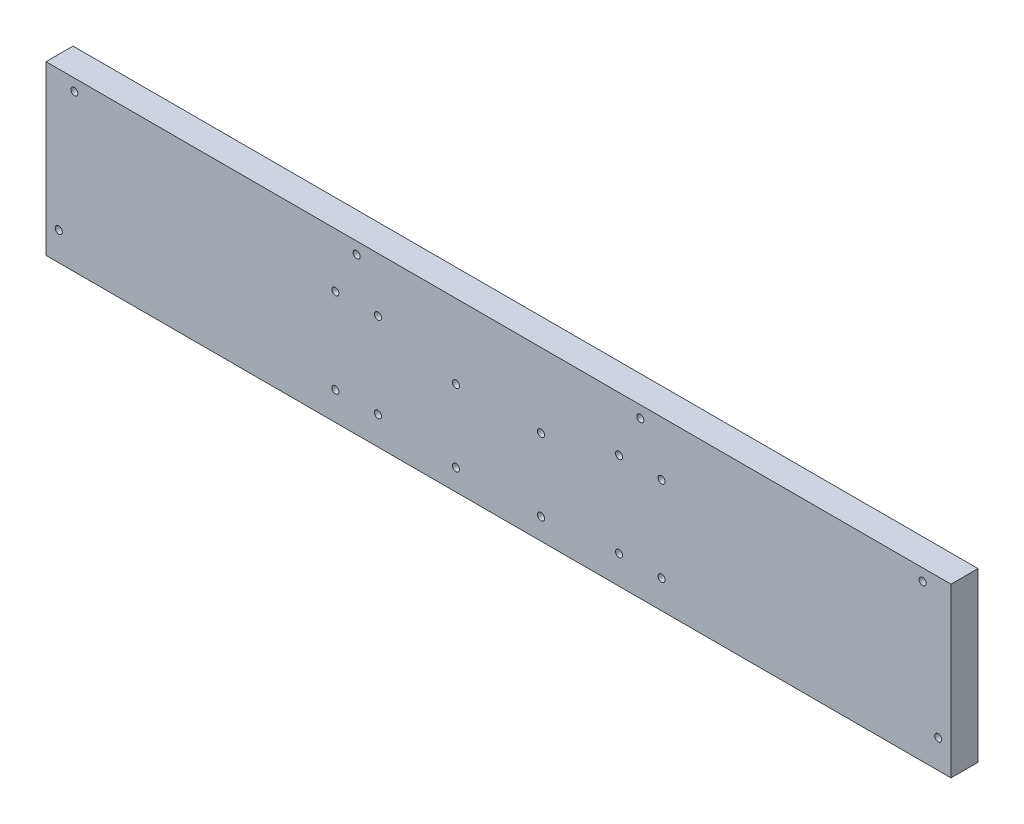
SolidWorks part; units mm, degrees
ref_plane "Front Plane" through (0, 0, 0) normal (0, 0, 1) x (1, 0, 0)
ref_plane "Top Plane" through (0, 0, 0) normal (0, 1, 0) x (1, 0, 0)
ref_plane "Right Plane" through (0, 0, 0) normal (1, 0, 0) x (0, 0, -1)
sketch "Sketch1" plane through (0, 0, 0) normal (0, 0, 1) x (1, 0, 0)
  line L1 (0, 118.3) -> (-638.1, 118.3)
  line L2 (0, 118.3) -> (0, 0)
  line L3 (0, 0) -> (-638.1, 0)
  line L4 (-638.1, 118.3) -> (-638.1, 0)
  dimension "D1" = 118.3
  dimension "D2" = 638.1
extrude "Boss-Extrude1" add sketch "Sketch1" along normal blind 19.05
sketch "Sketch4" plane through (0, 0, 19.05) normal (0, 0, 1) x (1, 0, 0)
  line L0 (-638.1, 0) -> (-638.1, 118.3)
  line L1 (-319.05, 0) -> (-319.05, 58.68)
  line L2 (-638.1, 0) -> (0, 0) construction
  line L3 (-638.1, 59.15) -> (0, 59.15)
  line L4 (0, 0) -> (0, 118.3) construction
  circle A6 centre (-9, 20) radius 2.5
  circle A7 centre (-20, 110.05) radius 2.5
  circle A8 centre (-219.05, 110.05) radius 2.5
  circle A9 centre (-419.05, 110.05) radius 2.5
  circle A10 centre (-618.1, 110.05) radius 2.5
  circle A11 centre (-629.1, 20) radius 2.5
hole_wizard "Ø5.0mm Dowel Hole1" positions "Sketch2" profile "Sketch3" hole size "Ø5.0" standard "ANSI Metric"
sketch "Sketch2" plane through (0, 0, 0) normal (0, 0, -1) x (-1, 0, 0)
  point P0 (434.05, 20)
  point P3 (404.05, 20)
  point P6 (404.05, 80)
  point P9 (434.05, 80)
  point P12 (349.05, 15)
  point P15 (349.05, 66)
  point P18 (289.05, 66)
  point P25 (289.05, 15)
  point P28 (234.05, 20)
  point P31 (234.05, 80)
  point P34 (204.05, 80)
  point P37 (204.05, 20)
  point P40 (629.1, 20)
  point P43 (618.1, 110.05)
  point P46 (419.05, 110.05)
  point P49 (219.05, 110.05)
  point P52 (20, 110.05)
  point P55 (9, 20)
sketch "Sketch3" plane through (-434.05, 20, 0) normal (1, 0, 0) x (0, 1, 0)
  line L0 (0, 0) -> (0, 30)
  line L1 (0, 30) -> (2.5, 28.4978)
  line L2 (2.5, 28.4978) -> (2.5, 0)
  line L5 (2.5, 0) -> (0, 0)
  line L10 (0, 30) -> (-2.5, 28.4978) construction
  line L11 (0, -6.35) -> (0, 107.95) construction
  dimension "Hole Dia." = 5
  dimension "Hole Depth" = 30
  dimension "Drill Angle" = 118
